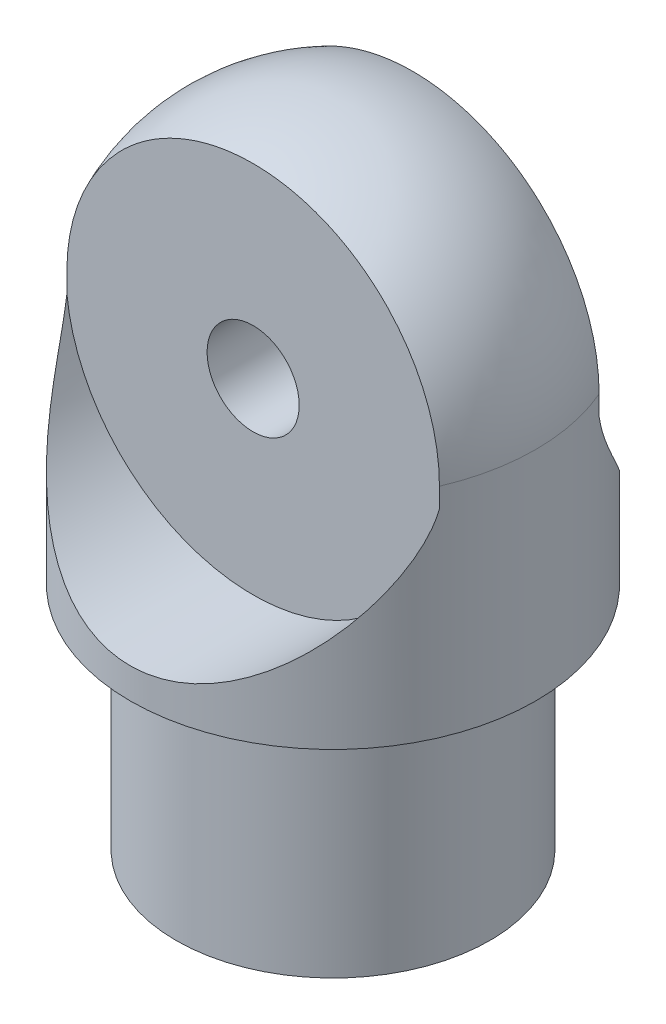
SolidWorks part; units mm, degrees
ref_plane "Front Plane" through (0, 0, 0) normal (0, 0, 1) x (1, 0, 0)
ref_plane "Top Plane" through (0, 0, 0) normal (0, 1, 0) x (1, 0, 0)
ref_plane "Right Plane" through (0, 0, 0) normal (1, 0, 0) x (0, 0, -1)
sketch "Sketch1" plane through (0, 0, 0) normal (0, 1, 0) x (1, 0, 0)
  circle A0 centre (0, 0) radius 12.9794
  dimension "D1" = 25.9588
extrude "Boss-Extrude1" add sketch "Sketch1" along normal blind 19.05
sketch "Sketch2" plane through (0, 0, 0) normal (1, 0, 0) x (0, 0, -1)
  line L0 (0, 10.4775) -> (0, -10.4775) construction
  line L3 (12.9794, 19.05) -> (-12.9794, 19.05) construction
  line L4 (0, 19.05) -> (0, 53.8256)
  line L5 (-16.764, 37.0616) -> (-16.764, 19.05)
  line L6 (-16.764, 19.05) -> (0, 19.05)
  arc A0 (0, 53.8256) -> (-16.764, 37.0616) centre (0, 37.0616) ccw
  dimension "D3" = 33.528
revolve "Revolve1" add sketch "Sketch2" angle 360 about L4
sketch "Sketch4" plane through (0, 0, 0) normal (0, 0, 1) x (1, 0, 0)
  line L0 (16.764, 37.0616) -> (-16.764, 37.0616) construction
  circle A0 centre (0, 37.0616) radius 3.81
  dimension "D1" = 7.62
extrude "Cut-Extrude1" cut sketch "Sketch4" against normal through all both and the other way through all
ref_axis "Axis1" through (0, 37.0616, -16.764) along (0, 0, 1)
ref_plane "Plane1" through (0, 0, -6.604) normal (0, 0, 1) x (1, 0, 0)
sketch "Sketch5" plane through (0, 0, -6.604) normal (0, 0, 1) x (1, 0, 0)
  circle A0 centre (0, 37.0616) radius 15.494
  dimension "D1" = 30.988
extrude "Cut-Extrude2" cut sketch "Sketch5" against normal blind 28.194
mirror "Mirror1" about plane through (0, 0, 0) normal (0, 0, 1) of "Cut-Extrude2"
